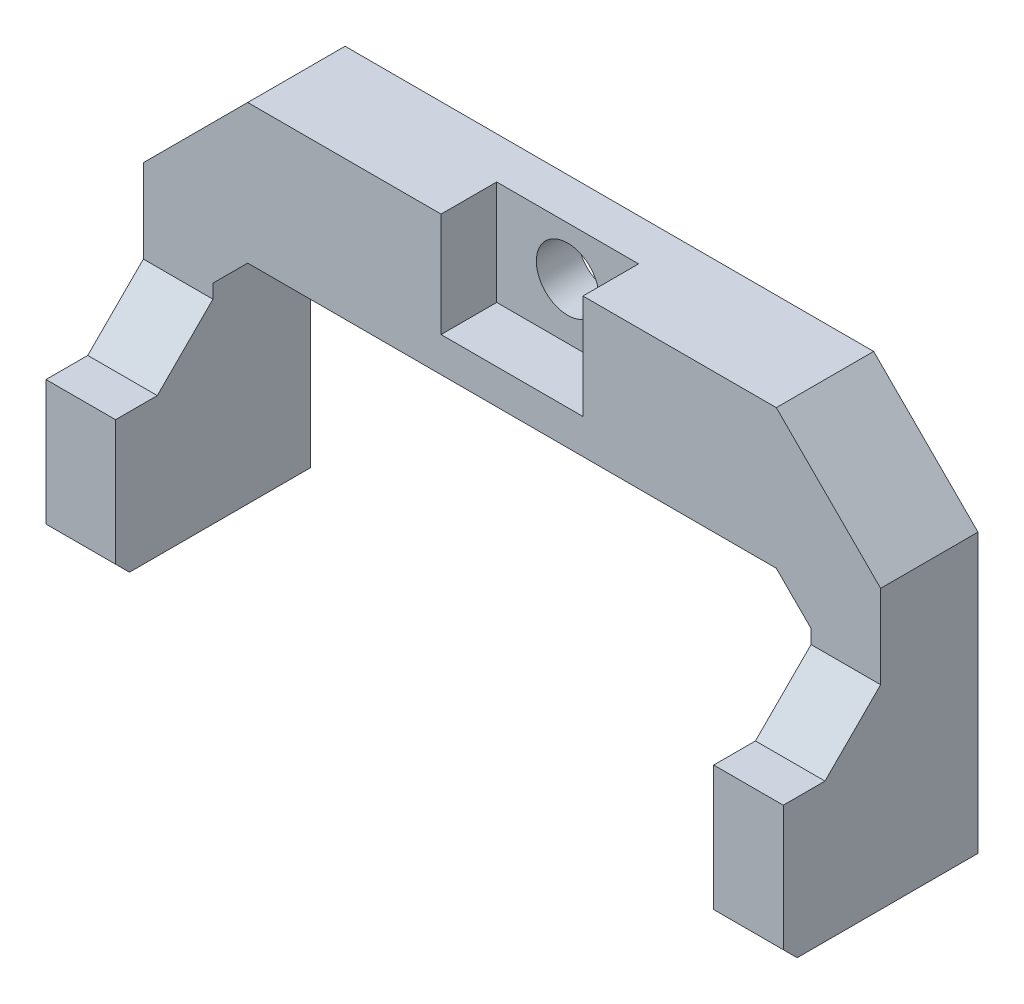
SolidWorks part; units mm, degrees
ref_plane "Front Plane" through (0, 0, 0) normal (0, 0, 1) x (1, 0, 0)
ref_plane "Top Plane" through (0, 0, 0) normal (0, 1, 0) x (1, 0, 0)
ref_plane "Right Plane" through (0, 0, 0) normal (1, 0, 0) x (0, 0, -1)
sketch "Sketch1" plane through (0, 0, 0) normal (0, 0, 1) x (1, 0, 0)
  line L0 (0, 0) -> (0, -10)
  line L1 (0, -10) -> (-19, -10)
  line L2 (-19, -10) -> (-21.5, -12.5)
  line L3 (-21.5, -12.5) -> (-21.5, -27.5)
  line L4 (-21.5, -27.5) -> (-26.5, -27.5)
  line L5 (-26.5, -27.5) -> (-26.5, -7.5)
  line L6 (-26.5, -7.5) -> (-19, 0)
  line L7 (-19, 0) -> (0, 0)
  dimension "D1" = 135
  dimension "D2" = 21.5
  dimension "D3" = 5
  dimension "D4" = 15
  dimension "D5" = 10
  dimension "D6" = 2.5
extrude "Boss-Extrude1" add sketch "Sketch1" along normal blind 7
sketch "Sketch6" plane through (0, 0, 7) normal (0, 0, 1) x (1, 0, 0)
  line L0 (-21.5, -27.5) -> (-21.5, -12.5) construction
  line L1 (-26.5, -27.5) -> (-21.5, -27.5)
  line L2 (-26.5, -27.5) -> (-26.5, -17.5)
  line L3 (-26.5, -17.5) -> (-21.5, -17.5)
  line L4 (-21.5, -27.5) -> (-21.5, -17.5)
  dimension "D1" = 10
extrude "Boss-Extrude2" add sketch "Sketch6" along normal blind 7
sketch "Sketch3" plane through (0, 0, 7) normal (0, 0, 1) x (1, 0, 0)
  line L1 (0, 0) -> (-5.1, 0)
  line L2 (0, 0) -> (0, -7.5)
  line L3 (0, -7.5) -> (-5.1, -7.5)
  line L4 (-5.1, 0) -> (-5.1, -7.5)
  dimension "D1" = 7.5
  dimension "D2" = 5.1
extrude "Cut-Extrude1" cut sketch "Sketch3" against normal blind 4
mirror "Mirror1" about plane through (0, 0, 7) normal (-1, 0, 0) of "Boss-Extrude2", "Boss-Extrude1", "Cut-Extrude1"
hole_wizard "M4 Clearance Hole1" positions "Sketch4" profile "Sketch5" hole size "M4" standard "ANSI Metric" end condition through all
sketch "Sketch4" plane through (0, 0, 3) normal (0, 0, 1) x (1, 0, 0)
  line L0 (-5.1, -7.5) -> (5.1, -7.5) construction
  line L1 (0, -55) -> (0, 55) construction
  point P0 (0, -3.5)
  dimension "D1" = 4
sketch "Sketch5" plane through (0, -3.5, 3) normal (1, 0, 0) x (0, -1, 0)
  line L0 (0, 0) -> (0, 3)
  line L1 (0, 3) -> (2.25, 3)
  line L2 (2.25, 3) -> (2.25, 0)
  line L5 (2.25, 0) -> (0, 0)
  line L11 (0, -6.35) -> (0, 107.95) construction
  dimension "Thru Hole Dia." = 4.5
  dimension "Thru Hole Depth" = 3
chamfer "Chamfer2" distance 4 2 edges at (24, -17.5, 7) (-24, -17.5, 7)
chamfer "Chamfer3" distance 1 angle 45 2 edges at (24, -27.5, 14) (-24, -27.5, 14)
equation "\"a\"=1"
